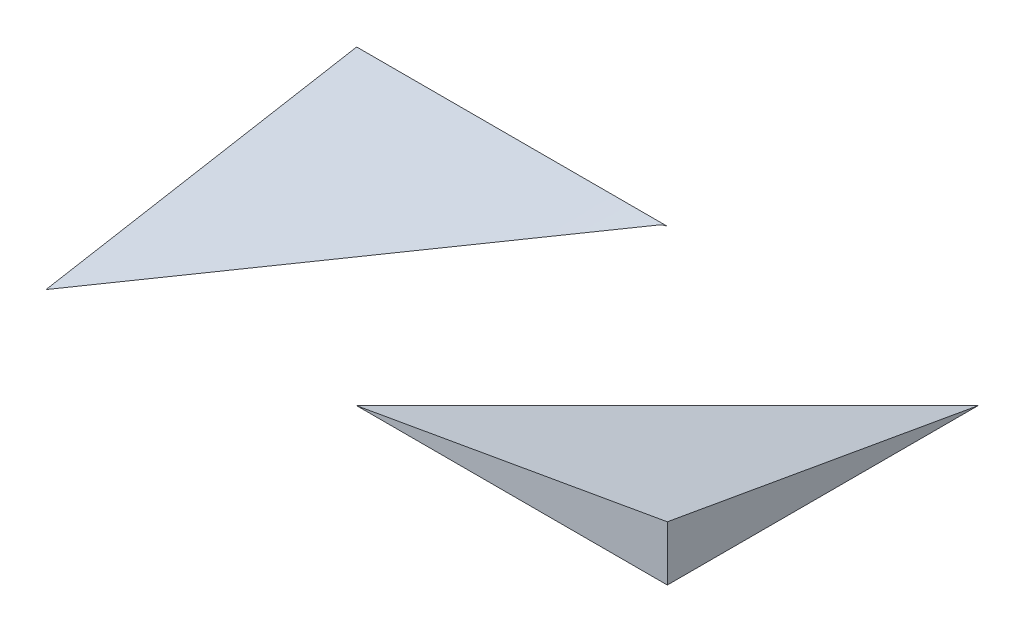
SolidWorks part; units mm, degrees
ref_plane "Front Plane" through (0, 0, 0) normal (0, 0, 1) x (1, 0, 0)
ref_plane "Top Plane" through (0, 0, 0) normal (0, 1, 0) x (1, 0, 0)
ref_plane "Right Plane" through (0, 0, 0) normal (1, 0, 0) x (0, 0, -1)
ref_axis "Axis1" through (0, 0, -88.99) along (0, 0, 1)
ref_plane "Plane1" through (0, 0, 0) normal (-0.1736, 0.9848, 0) x (0, 0, 1)
sketch "Sketch1" plane through (0, 0, 0) normal (0, 0, 1) x (1, 0, 0)
  line L0 (0, 0) -> (172.3414, 30.3884)
  line L1 (112.1373, 19.7728) -> (-112.1373, -19.7728) construction
  line L2 (172.3414, 30.3884) -> (172.3414, 0)
  line L3 (16.7136, 0) -> (-16.7136, 0) construction
  line L9 (0, 0) -> (172.3414, 0)
  dimension "D1" = 175
sketch "Sketch3" plane through (0, 0, 0) normal (0, 1, 0) x (1, 0, 0)
  line L0 (172.3414, 0) -> (172.3414, 172.3414)
  line L1 (0, 0) -> (172.3414, 0) construction
  line L2 (-55, 0) -> (55, 0) construction
  line L3 (172.3414, 172.3414) -> (0, 0)
  line L4 (0, 0) -> (172.3414, 0)
  dimension "D2" = 45
loft "Loft1" add profiles "Sketch3", "Sketch1" connector at (172.3414, 0, -172.3414) connector at (172.3414, 30.3884, 0)
ref_plane "Plane2" through (0, 0, -172.3414) normal (0, 0, 1) x (1, 0, 0)
sketch "Sketch4" plane through (0, 0, -172.3414) normal (0, 0, 1) x (1, 0, 0)
  line L3 (-172.3414, 0) -> (-172.3414, -30.3884)
  line L7 (94.7933, 0) -> (-94.7933, 0) construction
  line L8 (-172.3414, -30.3884) -> (0, 0)
  line L9 (0, 0) -> (-172.3414, 0)
  line L13 (112.1373, 19.7728) -> (-112.1373, -19.7728) construction
  dimension "D1" = 175
sketch "Sketch5" [suppressed] plane through (0, 0, 0) normal (0, 1, 0) x (1, 0, 0)
  line L1 (-172.3414, 0) -> (-172.3414, 172.3414)
  line L2 (0, 172.3414) -> (-172.3414, 172.3414) construction
  line L3 (-172.3414, 0) -> (0, 172.3414)
  line L5 (-172.3414, 172.3414) -> (0, 172.3414) construction
  line L6 (0, -33.43) -> (0, 33.43) construction
  line L8 (-33.43, 172.3414) -> (33.43, 172.3414) construction
  line L11 (-172.3414, 172.3414) -> (0, 172.3414)
ref_axis "Axis2" through (0, -1.5249, 0) along (0, 1, 0)
sketch "Sketch6" plane through (0, 0, 0) normal (-0.1736, 0.9848, 0) x (0, 0, 1)
  line L0 (-172.3414, -2.6586) -> (0, -175)
  line L1 (-172.3414, -175) -> (-172.3414, 0) construction
  line L2 (-172.3414, -175) -> (0, -175)
  line L3 (-172.3414, -175) -> (-172.3414, -2.6586)
  line L5 (0, -16.7191) -> (0, 16.7191) construction
  point P4 (-172.3414, -175)
  point P7 (-172.3414, -175)
  dimension "D1" = 45
loft "Loft3" add profiles "Sketch6", "Sketch4" connector at (-172.3414, -30.3884, -172.3414) connector at (-172.3414, -30.3884, -172.3414)
